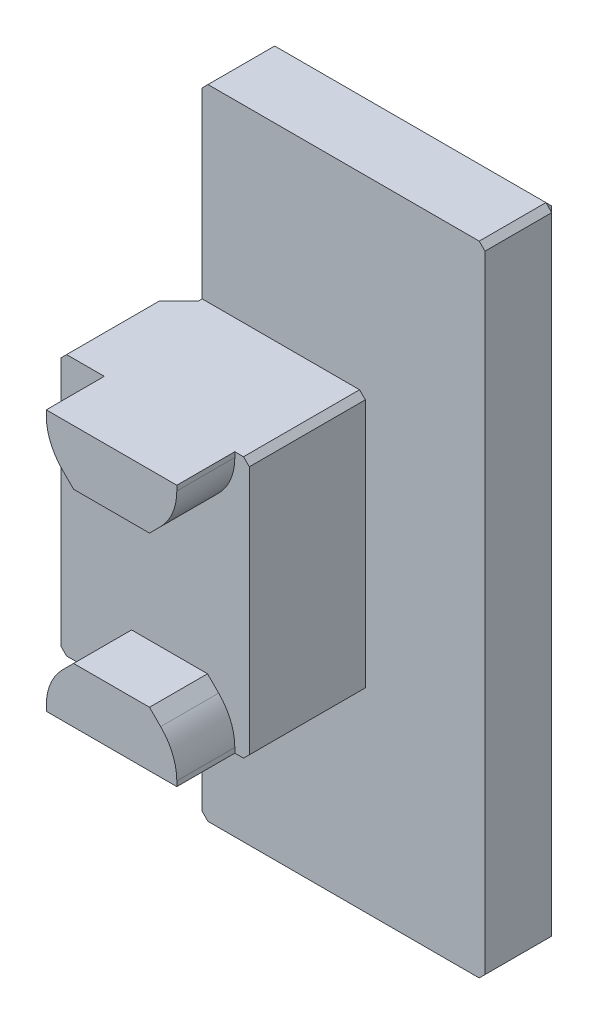
SolidWorks part; units mm, degrees
ref_plane "Front" through (0, 0, 0) normal (0, 0, 1) x (1, 0, 0)
ref_plane "Top" through (0, 0, 0) normal (0, 1, 0) x (1, 0, 0)
ref_plane "Right" through (0, 0, 0) normal (1, 0, 0) x (0, 0, -1)
sketch "Sketch1" plane through (0, 0, 0) normal (0, 0, 1) x (1, 0, 0)
  line L0 (-2.75, -11.5) -> (-2.75, -5) construction
  line L1 (2.75, -4.5) -> (-2.75, -4.5)
  line L2 (2.75, -4.5) -> (2.75, 4.5)
  line L3 (2.75, 4.5) -> (-2.75, 4.5)
  line L4 (-2.75, -4.5) -> (-2.75, 4.5) construction
  line L5 (2.75, -4.5) -> (-2.75, 4.5) construction
  line L6 (2.75, 4.5) -> (-2.75, -4.5) construction
  line L7 (-2.35, -4.5) -> (-3.75, -4.5) construction
  line L8 (-2.75, 4.5) -> (-3.75, 4.5)
  line L9 (-3.75, 4.5) -> (-3.75, -4.5)
  line L10 (-3.75, -4.5) -> (-2.75, -4.5)
  point P0 (0, 0)
extrude "Boss-Extrude1" add sketch "Sketch1" against normal blind 2
sketch "Sketch2" plane through (0, 0, 0) normal (0, 0, 1) x (1, 0, 0)
  line L0 (-2.25, -4.3284) -> (-2.25, -4.5)
  line L1 (-1.6935, -6.5151) -> (-1.3086, -6.9) construction
  line L2 (-1.3086, -6.9) -> (1.3086, -6.9) construction
  line L3 (1.3086, -6.9) -> (1.6935, -6.5151) construction
  line L4 (2.25, -5.1716) -> (2.25, -4.3284) construction
  line L5 (1.6935, -2.9849) -> (1.3086, -2.6)
  line L6 (1.3086, -2.6) -> (-1.3086, -2.6)
  line L7 (-1.3086, -2.6) -> (-1.6935, -2.9849)
  line L8 (-2.25, -4.3284) -> (-2.25, -5.1716) construction
  line L9 (1.35, -7) -> (1.7642, -6.5858)
  line L10 (-1.35, -7) -> (1.35, -7)
  line L11 (-1.7642, -6.5858) -> (-1.35, -7)
  line L12 (-2.35, -4.3284) -> (-2.35, -5.1716)
  line L13 (-1.35, -2.5) -> (-1.7642, -2.9142)
  line L14 (1.35, -2.5) -> (-1.35, -2.5)
  line L15 (1.7642, -2.9142) -> (1.35, -2.5)
  line L16 (2.35, -5.1716) -> (2.35, -4.3284)
  line L17 (1.35, -7) -> (1.7642, -6.5858) construction
  line L18 (-1.35, -7) -> (1.35, -7) construction
  line L20 (-1.7642, -6.5858) -> (-1.35, -7) construction
  line L22 (-2.35, -4.3284) -> (-2.35, -5.1716) construction
  line L24 (-1.35, -2.5) -> (-1.7642, -2.9142) construction
  line L26 (1.35, -2.5) -> (-1.35, -2.5) construction
  line L28 (1.7642, -2.9142) -> (1.35, -2.5) construction
  line L30 (2.35, -5.1716) -> (2.35, -4.3284) construction
  line L32 (2.25, -4.3284) -> (2.25, -4.5)
  line L39 (-2.75, -4.5) -> (2.75, -4.5)
  line L40 (-3.75, -4.5) -> (-2.75, -4.5)
  line L41 (-3.75, 4.5) -> (-3.75, -4.5)
  line L46 (-2.75, 4.5) -> (-3.75, 4.5)
  line L48 (2.75, 4.5) -> (-2.75, 4.5)
  line L54 (2.75, -4.5) -> (2.75, 4.5)
  line L58 (-2.25, -4.5) -> (2.25, -4.5)
  arc A0 (-2.25, -5.1716) -> (-1.6935, -6.5151) centre (-0.35, -5.1716) ccw construction
  arc A2 (1.6935, -6.5151) -> (2.25, -5.1716) centre (0.35, -5.1716) ccw construction
  arc A4 (2.25, -4.3284) -> (1.6935, -2.9849) centre (0.35, -4.3284) ccw
  arc A5 (-1.6935, -2.9849) -> (-2.25, -4.3284) centre (-0.35, -4.3284) ccw
  arc A7 (-2.35, -5.1716) -> (-1.7642, -6.5858) centre (-0.35, -5.1716) ccw
  arc A8 (-1.7642, -2.9142) -> (-2.35, -4.3284) centre (-0.35, -4.3284) ccw
  arc A10 (2.35, -4.3284) -> (1.7642, -2.9142) centre (0.35, -4.3284) ccw
  arc A11 (1.7642, -6.5858) -> (2.35, -5.1716) centre (0.35, -5.1716) ccw
  arc A12 (-2.35, -5.1716) -> (-1.7642, -6.5858) centre (-0.35, -5.1716) ccw construction
  arc A13 (-1.7642, -2.9142) -> (-2.35, -4.3284) centre (-0.35, -4.3284) ccw construction
  arc A14 (2.35, -4.3284) -> (1.7642, -2.9142) centre (0.35, -4.3284) ccw construction
  arc A15 (1.7642, -6.5858) -> (2.35, -5.1716) centre (0.35, -5.1716) ccw construction
  dimension "D1" = 0
  dimension "D2" = 0.1
  dimension "D3" = 0
extrude "Slot Tab" add sketch "Sketch2" along normal blind 2 contours L7 A5 L0 L58 L32 A4 L5 L6 region at (0, -3.6243, 0)
mirror "Slot Tabs" about plane through (0, 0, 0) normal (0, 1, 0) of "Slot Tab"
chamfer "Deburs" [suppressed] distance 0.2 angle 45
sketch "Sketch3" plane through (0, 0, -2) normal (0, 0, -1) x (-1, 0, 0)
  line L4 (3.75, 4.5) -> (-2.75, 4.5)
  line L5 (-2.75, 4.5) -> (-2.75, -4.5)
  line L6 (-2.75, -4.5) -> (3.75, -4.5)
  line L7 (3.75, -4.5) -> (3.75, 4.5)
  line L8 (3.75, 4.5) -> (-2.75, 4.5)
  line L9 (-2.75, 4.5) -> (-2.75, -4.5)
  line L10 (-2.75, -4.5) -> (3.75, -4.5)
  line L11 (3.75, -4.5) -> (3.75, 4.5)
  dimension "D1" = 0
extrude "Stopper Clearance" add sketch "Sketch3" along normal blind 2
sketch "Sketch4" plane through (0, 0, -4) normal (0, 0, -1) x (-1, 0, 0)
  line L1 (2.875, -11) -> (-6.875, -11)
  line L2 (2.875, -11) -> (2.875, 11)
  line L3 (2.875, 11) -> (-6.875, 11)
  line L4 (-6.875, -11) -> (-6.875, 11)
  line L5 (2.875, -11) -> (-6.875, 11) construction
  line L6 (2.875, 11) -> (-6.875, -11) construction
  point P0 (-2, 0)
  dimension "D1" = 2
  dimension "D2" = 22
  dimension "D3" = 9.75
extrude "Stopper" add sketch "Sketch4" along normal blind 2.5
chamfer "Deburs 2" distance 0.2 angle 45 12 edges at (2.75, 4.5, -2) (2.75, -4.5, -2) (-3.75, -4.5, -2) (-3.75, 4.5, -2) (2, 11, -6.5) (-2.875, 11, -5.25) (-2.875, 0, -6.5) (6.875, 11, -5.25) (6.875, 0, -6.5) (6.875, -11, -5.25) (2, -11, -6.5) (-2.875, -11, -5.25)
chamfer "Chamfer3" distance 1 angle 45 1 edges at (-3.75, 0, -4)
